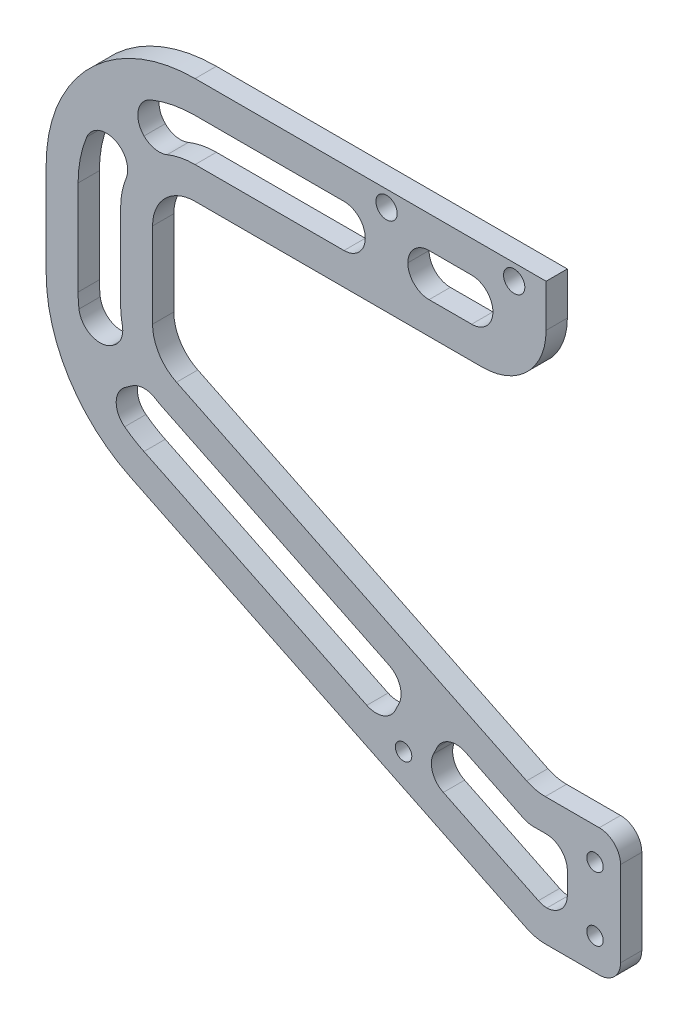
SolidWorks part; units mm, degrees
material "6061 Alloy"
ref_plane "Front Plane" through (0, 0, 0) normal (0, 0, 1) x (1, 0, 0)
ref_plane "Top Plane" through (0, 0, 0) normal (0, 1, 0) x (1, 0, 0)
ref_plane "Right Plane" through (0, 0, 0) normal (1, 0, 0) x (0, 0, -1)
sketch "Sketch1" plane through (0, 0, 0) normal (0, 0, 1) x (1, 0, 0)
  line L0 (0, 0) -> (0, 38.1)
  line L1 (0, 38.1) -> (-25.4, 38.1)
  line L2 (-139.7, 101.6) -> (-139.7, 127)
  line L3 (-127, 139.7) -> (-22.225, 139.7)
  line L4 (-22.225, 139.7) -> (-22.225, 171.45)
  line L5 (-22.225, 171.45) -> (-127, 171.45)
  line L6 (-171.45, 127) -> (-171.45, 98.8013)
  line L7 (0, 0) -> (-25.4, 0)
  line L8 (-146.4302, 58.8229) -> (-25.4, 0)
  line L9 (0, 19.05) -> (25.4, 19.05) construction
  line L10 (25.4, 19.05) -> (25.4, 120.65) construction
  line L11 (25.4, 120.65) -> (-127, 120.65) construction
  line L12 (-25.4, 38.1) -> (-132.5515, 90.1776)
  line L13 (0, 19.05) -> (-7.62, 19.05) construction
  line L14 (-7.62, 28.575) -> (-7.62, 9.525) construction
  line L15 (-7.62, 28.575) -> (-64.77, 28.575) construction
  line L16 (-69.85, 166.6875) -> (-31.75, 166.6875) construction
  line L17 (-50.8, 166.6875) -> (-50.8, 120.65) construction
  line L18 (-127, 120.65) -> (-127, 101.6) construction
  arc A0 (-171.45, 98.8013) -> (-146.4302, 58.8229) centre (-127, 98.8013) ccw
  arc A1 (-127, 171.45) -> (-171.45, 127) centre (-127, 127) ccw
  arc A2 (-139.7, 127) -> (-127, 139.7) centre (-127, 127) cw
  arc A3 (-132.5515, 90.1776) -> (-139.7, 101.6) centre (-127, 101.6) cw
  circle A7 centre (-31.75, 166.6875) radius 3.175 construction
  circle A8 centre (-69.85, 166.6875) radius 3.175 construction
  point P26 (-50.8, 166.6875)
  point P28 (-50.8, 120.65)
  dimension "D9" = 44.45
  dimension "D10" = 12.7
  dimension "D22" = 6.35
  dimension "D8" = 44.45
  dimension "D1" = 38.1
  dimension "D3" = 31.75
  dimension "D4" = 31.75
  dimension "D5" = 19.05
  dimension "D6" = 19.05
  dimension "D7" = 57.15
  dimension "D11" = 25.4
  dimension "D12" = 101.6
  dimension "D13" = 152.4
  dimension "D14" = 25.4
  dimension "D15" = 19.05
  dimension "D17" = 7.62
  dimension "D19" = 4.7625
  dimension "D20" = 38.1
  dimension "D21" = 9.525
extrude "Boss-Extrude1" add sketch "Sketch1" along normal blind 6.35
hole_wizard "1/4 (0.25) Diameter Hole1" positions "Sketch3" profile "Sketch2" hole size "1/4" standard "ANSI Inch"
sketch "Sketch3" plane through (0, 0, 6.35) normal (0, 0, 1) x (1, 0, 0)
  line L0 (-69.85, 166.6875) -> (-22.225, 166.6875) construction
  line L1 (-22.225, 139.7) -> (-22.225, 171.45) construction
  line L3 (-22.225, 171.45) -> (-127, 171.45) construction
  point P4 (-69.85, 166.6875)
  point P6 (-31.75, 166.6875)
  dimension "D1" = 9.525
  dimension "D2" = 38.1
  dimension "D3" = 4.7625
sketch "Sketch2" plane through (-69.85, 166.6875, 6.35) normal (1, 0, 0) x (0, -1, 0)
  line L0 (0, 0) -> (0, 11.5597)
  line L1 (0, 11.5597) -> (3.175, 9.652)
  line L2 (3.175, 9.652) -> (3.175, 0)
  line L5 (3.175, 0) -> (0, 0)
  line L10 (0, 11.5597) -> (-3.175, 9.652) construction
  line L11 (0, -6.35) -> (0, 107.95) construction
  dimension "Hole Dia." = 6.35
  dimension "Hole Depth" = 9.652
  dimension "Drill Angle" = 118
hole_wizard "#10 (0.1935) Diameter Hole1" positions "Sketch5" profile "Sketch4" hole size "#10" standard "ANSI Inch"
sketch "Sketch5" plane through (0, 0, 6.35) normal (0, 0, 1) x (1, 0, 0)
  line L0 (-7.62, 28.575) -> (-7.62, 9.525) construction
  line L2 (0, 19.05) -> (-7.62, 19.05) construction
  line L3 (0, 0) -> (0, 38.1) construction
  line L6 (-64.77, 28.575) -> (-7.62, 28.575) construction
  point P0 (-7.62, 28.575)
  point P2 (-7.62, 9.525)
  point P18 (-64.77, 28.575)
  dimension "D1" = 19.05
  dimension "D2" = 7.62
  dimension "D3" = 57.15
sketch "Sketch4" plane through (-7.62, 28.575, 6.35) normal (1, 0, 0) x (0, -1, 0)
  line L0 (0, 0) -> (0, 11.1286)
  line L1 (0, 11.1286) -> (2.4574, 9.652)
  line L2 (2.4574, 9.652) -> (2.4574, 0)
  line L5 (2.4574, 0) -> (0, 0)
  line L10 (0, 11.1286) -> (-2.4575, 9.652) construction
  line L11 (0, -6.35) -> (0, 107.95) construction
  dimension "Hole Dia." = 4.9149
  dimension "Hole Depth" = 9.652
  dimension "Drill Angle" = 118
fillet "Fillet1" radius 12.7 2 edges at (-25.4, 0, 3.175) (-25.4, 38.1, 3.175)
fillet "Fillet2" radius 6.35 2 edges at (0, 0, 3.175) (0, 38.1, 3.175)
sketch "Sketch7" plane through (0, 0, 6.35) normal (0, 0, 1) x (1, 0, 0)
  line L0 (-12.7, 28.575) -> (-22.4772, 28.575)
  line L1 (-32.1924, 30.8108) -> (-51.9549, 40.4158)
  line L2 (-58.6067, 26.7295) -> (-23.8651, 9.8444)
  line L3 (-22.4772, 9.525) -> (-12.7, 9.525)
  line L4 (-12.7, 28.575) -> (-12.7, 9.525)
  line L5 (-58.6067, 26.7295) -> (-51.9549, 40.4158)
  line L6 (-32.1924, 30.8108) -> (-136.7151, 81.6108) construction
  line L7 (-142.2666, 67.3897) -> (-23.8651, 9.8444) construction
  line L8 (-22.4772, 9.525) -> (-6.35, 9.525) construction
  line L9 (-6.35, 28.575) -> (-22.4772, 28.575) construction
  line L10 (-22.4772, 0) -> (-6.35, 0)
  line L11 (0, 6.35) -> (0, 31.75)
  line L12 (-6.35, 38.1) -> (-22.4772, 38.1)
  line L13 (-28.0287, 39.3776) -> (-132.5515, 90.1776)
  line L14 (-139.7, 101.6) -> (-139.7, 127)
  line L15 (-127, 139.7) -> (-22.225, 139.7)
  line L16 (-22.225, 139.7) -> (-22.225, 171.45)
  line L17 (-22.225, 171.45) -> (-127, 171.45)
  line L18 (-171.45, 127) -> (-171.45, 98.8013)
  line L19 (-146.4302, 58.8229) -> (-28.0287, 1.2776)
  line L20 (-161.925, 133.35) -> (-161.925, 95.25)
  line L21 (0, 6.35) -> (0, 31.75) construction
  line L22 (-161.925, 95.25) -> (-149.225, 95.25)
  line L23 (-149.225, 133.35) -> (-149.225, 95.25)
  line L24 (-139.7, 101.6) -> (-139.7, 127) construction
  line L25 (-127, 139.7) -> (-22.225, 139.7) construction
  line L26 (-22.225, 139.7) -> (-22.225, 171.45) construction
  line L27 (-22.225, 171.45) -> (-127, 171.45) construction
  line L28 (-171.45, 127) -> (-171.45, 98.8013) construction
  line L29 (-149.225, 133.35) -> (-161.925, 133.35)
  line L30 (-133.35, 158.75) -> (-133.35, 146.05)
  line L31 (-133.35, 146.05) -> (-79.375, 146.05)
  line L32 (-79.375, 146.05) -> (-79.375, 158.75)
  line L33 (-28.0287, 39.3776) -> (-132.5515, 90.1776) construction
  line L34 (-28.0287, 39.3776) -> (-132.5515, 90.1776)
  line L35 (-79.375, 158.75) -> (-133.35, 158.75)
  line L36 (-28.0287, 39.3776) -> (-132.5515, 90.1776) construction
  line L37 (-146.4302, 58.8229) -> (-28.0287, 1.2776) construction
  line L38 (-22.4772, 0) -> (-6.35, 0) construction
  line L39 (-6.35, 38.1) -> (-22.4772, 38.1) construction
  line L40 (-60.325, 158.75) -> (-60.325, 146.05)
  line L41 (-60.325, 146.05) -> (-41.275, 146.05)
  line L42 (-41.275, 146.05) -> (-41.275, 158.75)
  line L43 (-41.275, 158.75) -> (-60.325, 158.75)
  line L49 (-131.9116, 79.2762) -> (-63.3773, 45.9673)
  line L50 (-63.3773, 45.9673) -> (-70.0291, 32.281)
  line L51 (-70.0291, 32.281) -> (-138.5634, 65.5899)
  line L52 (-138.5634, 65.5899) -> (-131.9116, 79.2762)
  line L53 (-146.4302, 58.8229) -> (-28.0287, 1.2776) construction
  line L54 (-58.6067, 26.7295) -> (-70.0291, 32.281) construction
  line L55 (-64.77, 28.575) -> (-53.5025, 51.7583) construction
  arc A0 (-32.1924, 30.8108) -> (-22.4772, 28.575) centre (-22.4772, 50.8) ccw
  arc A1 (-23.8651, 9.8444) -> (-22.4772, 9.525) centre (-22.4772, 12.7) ccw
  circle A2 centre (-69.85, 166.6875) radius 3.175 construction
  circle A3 centre (-31.75, 166.6875) radius 3.175 construction
  arc A8 (-6.35, 0) -> (0, 6.35) centre (-6.35, 6.35) ccw
  arc A9 (0, 31.75) -> (-6.35, 38.1) centre (-6.35, 31.75) ccw
  arc A10 (-28.0287, 39.3776) -> (-22.4772, 38.1) centre (-22.4772, 50.8) ccw
  arc A11 (-139.7, 101.6) -> (-132.5515, 90.1776) centre (-127, 101.6) ccw
  arc A12 (-127, 139.7) -> (-139.7, 127) centre (-127, 127) ccw
  arc A13 (-127, 171.45) -> (-171.45, 127) centre (-127, 127) ccw
  arc A14 (-171.45, 98.8013) -> (-146.4302, 58.8229) centre (-127, 98.8013) ccw
  arc A15 (-28.0287, 1.2776) -> (-22.4772, 0) centre (-22.4772, 12.7) ccw
  arc A16 (-6.35, 0) -> (0, 6.35) centre (-6.35, 6.35) ccw construction
  arc A17 (0, 31.75) -> (-6.35, 38.1) centre (-6.35, 31.75) ccw construction
  arc A18 (-28.0287, 39.3776) -> (-22.4772, 38.1) centre (-22.4772, 50.8) ccw construction
  arc A19 (-139.7, 101.6) -> (-132.5515, 90.1776) centre (-127, 101.6) ccw construction
  arc A20 (-127, 139.7) -> (-139.7, 127) centre (-127, 127) ccw construction
  arc A21 (-127, 171.45) -> (-171.45, 127) centre (-127, 127) ccw construction
  arc A22 (-171.45, 98.8013) -> (-146.4302, 58.8229) centre (-127, 98.8013) ccw construction
  arc A23 (-28.0287, 1.2776) -> (-22.4772, 0) centre (-22.4772, 12.7) ccw construction
  point P46 (-64.3179, 29.5052)
  point P63 (-149.225, 114.3)
  point P64 (-139.7, 114.3)
  dimension "D11" = 9.525
  dimension "D3" = 9.525
  dimension "D4" = 9.525
  dimension "D5" = 12.7
  dimension "D6" = 12.7
  dimension "D7" = 76.2
  dimension "D8" = 38.1
  dimension "D9" = 9.525
  dimension "D10" = 9.525
  dimension "D12" = 9.525
  dimension "D13" = 6.35
  dimension "D14" = 12.7
  dimension "D15" = 9.525
  dimension "D16" = 53.975
  dimension "D1" = 0
  dimension "D2" = 9.525
extrude "Cut-Extrude2" [suppressed] cut sketch "Sketch7" against normal up to next contours L52 L51 L50 L49 | L23 L29 L20 L22 | L32 L35 L30 L31 | L42 L43 L40 L41 | L5 L1 A0 L0 L4 L3 A1 L2
fillet "Fillet3" [suppressed] radius 6.35
sketch "Sketch8" plane through (0, 0, 6.35) normal (0, 0, 1) x (1, 0, 0)
  line L0 (-158.4309, 158.4309) -> (-135.9803, 135.9803) construction
  line L1 (-164.6794, 75.2203) -> (-137.4037, 94.3163) construction
  line L2 (-53.5025, 51.7583) -> (-68.4815, 20.9384) construction
  line L3 (-28.0287, 39.3776) -> (-132.5515, 90.1776) construction
  line L4 (-146.4302, 58.8229) -> (-28.0287, 1.2776) construction
  line L5 (-123.6324, 130.3676) -> (-130.3676, 123.6324) construction
  line L6 (-101.6, 171.45) -> (-101.6, 161.925) construction
  line L7 (-22.225, 171.45) -> (-127, 171.45) construction
  line L8 (-101.6, 139.7) -> (-101.6, 149.225) construction
  line L9 (-127, 139.7) -> (-22.225, 139.7) construction
  line L10 (-76.2, 161.925) -> (-127, 161.925)
  line L11 (-127, 149.225) -> (-76.2, 149.225)
  line L12 (-76.2, 149.225) -> (-76.2, 161.925)
  line L13 (-148.0974, 154.8326) -> (-138.9828, 145.718)
  line L14 (-69.85, 171.45) -> (-69.85, 139.7) construction
  line L15 (-31.75, 171.45) -> (-31.75, 139.7) construction
  line L16 (-161.925, 127) -> (-161.925, 98.8013)
  line L17 (-149.225, 127) -> (-149.225, 101.6)
  line L18 (-154.8326, 148.0974) -> (-145.718, 138.9828)
  line L19 (-153.5499, 88.8258) -> (-148.0871, 81.023) construction
  line L20 (-159.0667, 84.9635) -> (-147.515, 93.0509)
  line L21 (-142.0522, 85.2482) -> (-154.1221, 76.7979)
  line L22 (-136.7151, 81.6108) -> (-63.3773, 45.9673)
  line L23 (-142.2666, 67.3897) -> (-70.0291, 32.281)
  line L24 (-70.4812, 31.3507) -> (-59.0588, 25.7993) construction
  line L25 (-70.0291, 32.281) -> (-63.3773, 45.9673)
  line L26 (-76.2, 155.575) -> (-63.5, 155.575) construction
  line L27 (-51.9549, 40.4158) -> (-27.5921, 28.575)
  line L28 (-27.5921, 28.575) -> (-15.875, 28.575)
  line L29 (-15.875, 28.575) -> (-15.875, 9.525)
  line L30 (-15.875, 9.525) -> (-23.2079, 9.525)
  line L31 (-23.2079, 9.525) -> (-58.6067, 26.7295)
  line L32 (-58.6067, 26.7295) -> (-51.9549, 40.4158)
  line L34 (0, 6.35) -> (0, 31.75) construction
  line L35 (-15.875, 9.525) -> (-15.875, 0) construction
  line L36 (-22.4772, 0) -> (-6.35, 0) construction
  line L37 (-15.875, 28.575) -> (-15.875, 38.1) construction
  line L38 (-6.35, 38.1) -> (-22.4772, 38.1) construction
  line L39 (-38.1, 155.575) -> (-25.4, 155.575) construction
  line L41 (-63.5, 161.925) -> (-38.1, 161.925)
  line L42 (-63.5, 161.925) -> (-63.5, 149.225)
  line L43 (-63.5, 149.225) -> (-38.1, 149.225)
  line L44 (-38.1, 161.925) -> (-38.1, 149.225)
  arc A0 (-127, 171.45) -> (-171.45, 127) centre (-127, 127) ccw construction
  arc A1 (-127, 139.7) -> (-139.7, 127) centre (-127, 127) ccw construction
  arc A2 (-171.45, 98.8013) -> (-146.4302, 58.8229) centre (-127, 98.8013) ccw construction
  arc A3 (-139.7, 101.6) -> (-132.5515, 90.1776) centre (-127, 101.6) ccw construction
  arc A4 (-127, 149.225) -> (-138.9828, 145.718) centre (-127, 127) ccw
  arc A5 (-127, 161.925) -> (-148.0974, 154.8326) centre (-127, 127) ccw
  arc A6 (-145.718, 138.9828) -> (-149.225, 127) centre (-127, 127) ccw
  arc A7 (-154.8326, 148.0974) -> (-161.925, 127) centre (-127, 127) ccw
  arc A8 (-149.225, 101.6) -> (-147.515, 93.0509) centre (-127, 101.6) ccw
  arc A9 (-161.925, 98.8013) -> (-159.0667, 84.9635) centre (-127, 98.8013) ccw
  arc A10 (-142.0522, 85.2482) -> (-136.7151, 81.6108) centre (-127, 101.6) ccw
  arc A11 (-154.1221, 76.7979) -> (-142.2666, 67.3897) centre (-127, 98.8013) ccw
  point P8 (-127, 127)
  point P9 (-127, 127)
  point P18 (-127, 101.6)
  point P19 (-150.8185, 84.9244)
  point P26 (-64.77, 28.575)
  point P47 (-69.85, 166.6875)
  point P48 (-31.75, 166.6875)
  point P77 (-69.85, 155.575)
  point P94 (-31.75, 155.575)
  dimension "D1" = 9.525
  dimension "D2" = 9.525
  dimension "D3" = 12.7
  dimension "D4" = 12.7
  dimension "D5" = 15.875
extrude "Cut-Extrude3" cut sketch "Sketch8" against normal through all
fillet "Fillet4" radius 6.35 22 edges at (-27.5921, 28.575, 3.175) (-23.2079, 9.525, 3.175) (-15.875, 9.525, 3.175) (-15.875, 28.575, 3.175) (-58.6067, 26.7295, 3.175) (-51.9549, 40.4158, 3.175) (-63.3773, 45.9673, 3.175) (-70.0291, 32.281, 3.175) (-154.1221, 76.7979, 3.175) (-142.0522, 85.2482, 3.175) (-147.515, 93.0509, 3.175) (-159.0667, 84.9635, 3.175) (-154.8326, 148.0974, 3.175) (-145.718, 138.9828, 3.175) (-138.9828, 145.718, 3.175) (-148.0974, 154.8326, 3.175) (-76.2, 149.225, 3.175) (-76.2, 161.925, 3.175) (-38.1, 149.225, 3.175) (-38.1, 161.925, 3.175) (-63.5, 149.225, 3.175) (-63.5, 161.925, 3.175)
fillet "Fillet5" radius 19.05 1 edges at (-22.225, 139.7, 3.175)
